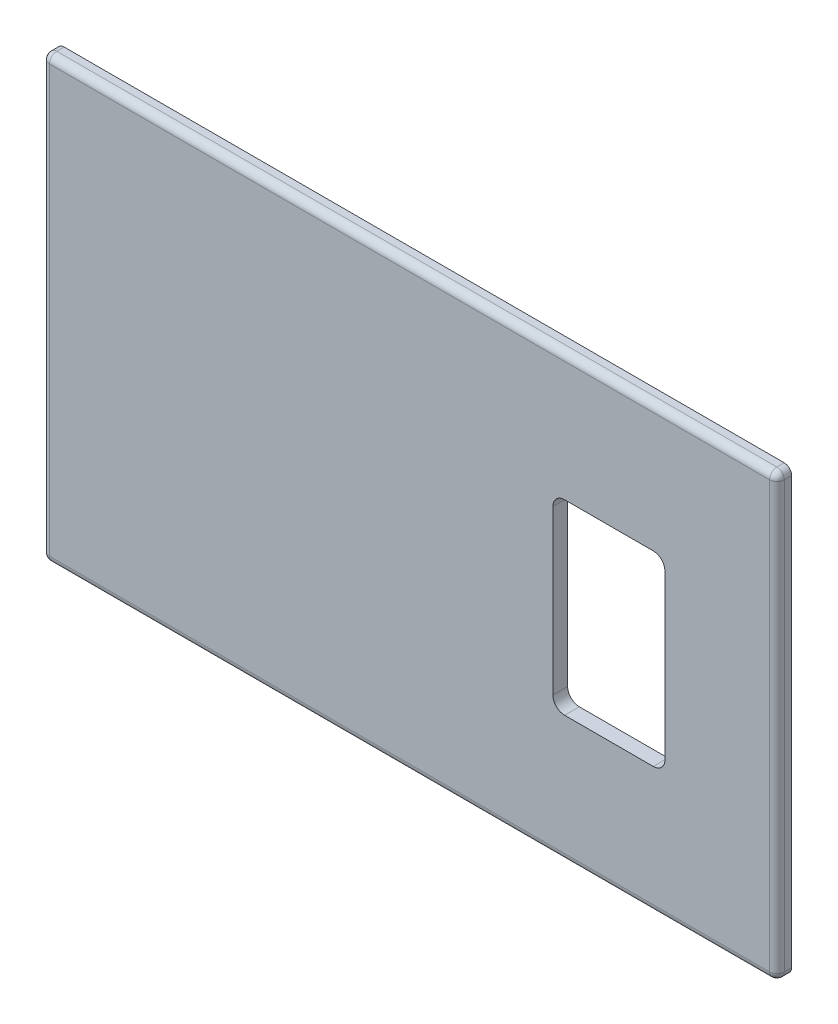
SolidWorks part; units mm, degrees
ref_plane "Front Plane" through (0, 0, 0) normal (0, 0, 1) x (1, 0, 0)
ref_plane "Top Plane" through (0, 0, 0) normal (0, 1, 0) x (1, 0, 0)
ref_plane "Right Plane" through (0, 0, 0) normal (1, 0, 0) x (0, 0, -1)
sketch "Sketch1" plane through (0, 0, 0) normal (0, 0, 1) x (1, 0, 0)
  line L1 (-50, -30) -> (50, -30)
  line L2 (-50, -30) -> (-50, 30)
  line L3 (-50, 30) -> (50, 30)
  line L4 (50, -30) -> (50, 30)
  line L5 (-50, -30) -> (50, 30) construction
  line L6 (-50, 30) -> (50, -30) construction
  point P0 (0, 0)
  dimension "D1" = 100
  dimension "D2" = 60
extrude "Boss-Extrude1" add sketch "Sketch1" along normal blind 2 contours L2 L3 L4 L1
fillet "Fillet1" radius 1 8 edges at (-50, 0, 2) (0, -30, 2) (50, 0, 2) (0, 30, 2) (50, 30, 1) (50, -30, 1) (-50, -30, 1) (-50, 30, 1)
sketch "Sketch2" plane through (0, 0, 2) normal (0, 0, 1) x (1, 0, 0)
  line L0 (27.14, 0) -> (0, 0) construction
  line L1 (34.76, 12.7) -> (19.52, 12.7)
  line L2 (34.76, 12.7) -> (34.76, -12.7)
  line L3 (34.76, -12.7) -> (19.52, -12.7)
  line L4 (19.52, 12.7) -> (19.52, -12.7)
  line L5 (34.76, 12.7) -> (19.52, -12.7) construction
  line L6 (34.76, -12.7) -> (19.52, 12.7) construction
  line L7 (50, -29) -> (50, 29) construction
  point P0 (27.14, 0)
  dimension "D1" = 25.4
  dimension "D2" = 15.24
  dimension "D4" = 15.24
extrude "Cut-Extrude1" cut sketch "Sketch2" against normal through all
fillet "Fillet2" radius 1.5875 4 edges at (19.52, 12.7, 1) (19.52, -12.7, 1) (34.76, -12.7, 1) (34.76, 12.7, 1)
ref_plane "Plane1" through (27.14, 0, 0) normal (-1, 0, 0) x (0, 0, 1)
